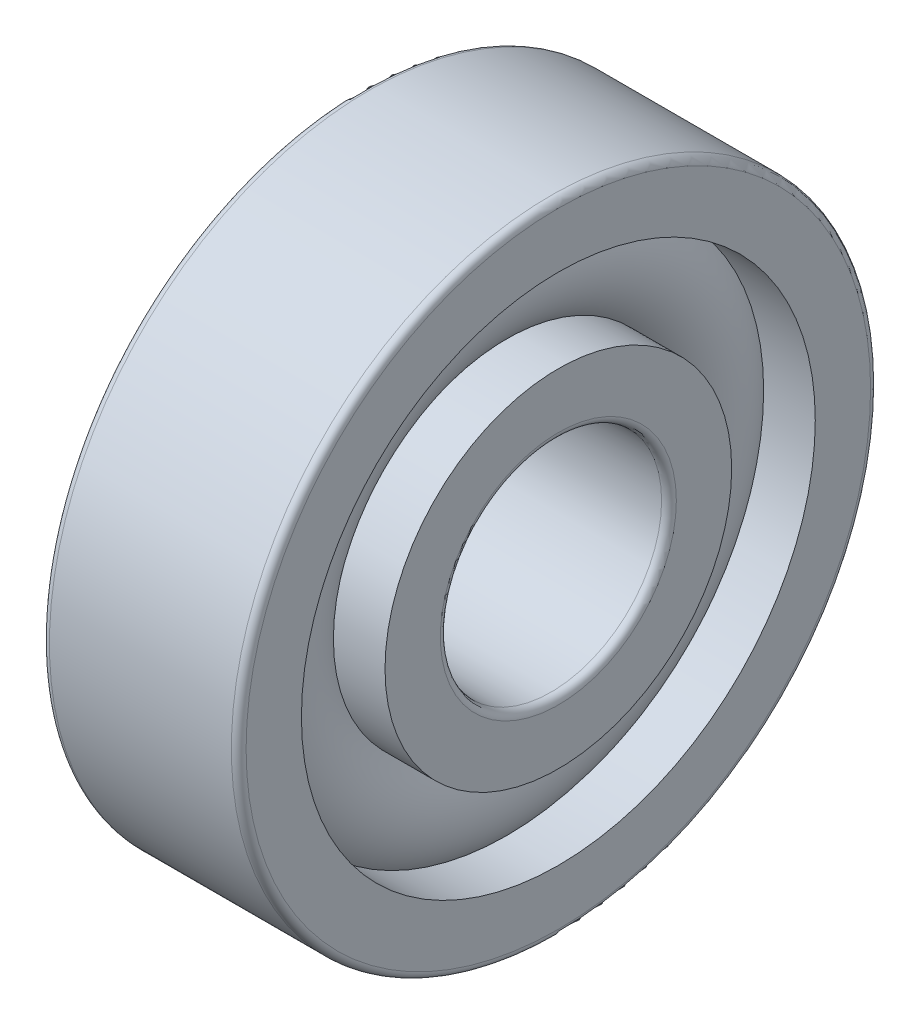
SolidWorks part; units mm, degrees
ref_plane "Plane1" through (0, 0, 0) normal (0, 0, 1) x (1, 0, 0)
ref_plane "Plane2" through (0, 0, 0) normal (0, 1, 0) x (1, 0, 0)
ref_plane "Plane3" through (0, 0, 0) normal (1, 0, 0) x (0, 0, -1)
other "Configuration Table"
sketch "Clipboard" plane through (0, 0, 0) normal (0, 0, 1) x (1, 0, 0)
  line L0 (-10, 0) -> (10, 0) construction
  line L1 (0, 0) -> (22.3471, -0.7804)
  line L2 (0, 0) -> (8.7447, 0.3054)
  line L3 (0, 0) -> (22.3471, -0.7804)
  line L4 (0, 0) -> (-22.3573, -0.3902)
  dimension "BallCLRad" = 8.75
sketch "CagSpiSke" plane through (0, 0, 0) normal (0, 0, 1) x (1, 0, 0)
  line L0 (0.255, 8.325) -> (0.255, 9.175)
  line L1 (0.255, 9.175) -> (-0.255, 9.175)
  line L2 (-0.255, 9.175) -> (-0.255, 8.325)
  line L3 (-0.255, 8.325) -> (0.255, 8.325)
  line L4 (-20.6375, 0) -> (20.6375, 0) construction
  line L5 (0, 0) -> (0, 23.7692) construction
  dimension "OD" = 18.35
  dimension "ID" = 16.65
revolve "CageSpine" add sketch "CagSpiSke" angle 0.001 about L4 reverse direction yes
ref_axis "Axis1" through (-50, 0, 0) along (1, 0, 0)
sketch "CagBalSke" plane through (0, 0, 0) normal (0, 0, 1) x (1, 0, 0)
  line L0 (-2.805, 8.75) -> (2.805, 8.75)
  line L1 (-1.905, 8.75) -> (1.905, 8.75) construction
  line L2 (-10, 0) -> (10, 0) construction
  line L3 (0, 0) -> (0, 24) construction
  arc A0 (2.805, 8.75) -> (-2.805, 8.75) centre (0, 8.75) cw
  dimension "BallCLRad" = 8.75
revolve "CageBall" [suppressed] add sketch "CagBalSke" angle 360 about L1 reverse direction yes
pattern_circular "CageBalls" [suppressed] count 2 every 180 about axis through (-50, 0, 0) along (1, 0, 0)
sketch "CagTrmODSke" plane through (0, 0, 0) normal (0, 0, 1) x (1, 0, 0)
  line L0 (2.806, 9.175) -> (2.806, 11.556)
  line L1 (2.806, 11.556) -> (-2.806, 11.556)
  line L2 (-2.806, 11.556) -> (-2.806, 9.175)
  line L3 (-2.806, 9.175) -> (2.806, 9.175)
  line L4 (-20.6375, 0) -> (20.6375, 0) construction
  line L5 (0, 0) -> (0, 25) construction
  dimension "Width" = 5.612
  dimension "ID" = 18.35
  dimension "OD" = 23.112
revolve "CageTrimOD" [suppressed] cut sketch "CagTrmODSke" angle 360 about L4 reverse direction yes
sketch "CagTrmIDSke" plane through (0, 0, 0) normal (0, 0, 1) x (1, 0, 0)
  line L0 (2.806, 5.946) -> (2.806, 8.325)
  line L1 (2.806, 8.325) -> (-2.806, 8.325)
  line L2 (-2.806, 8.325) -> (-2.806, 5.946)
  line L3 (-2.806, 5.946) -> (2.806, 5.946)
  line L4 (-20.6375, 0) -> (20.6375, 0) construction
  line L5 (0, 0) -> (0, 25) construction
  dimension "Width" = 5.612
  dimension "ID" = 11.892
  dimension "OD" = 16.65
revolve "CageTrimID" [suppressed] cut sketch "CagTrmIDSke" angle 360 about L4 reverse direction yes
sketch "BalSimSke" plane through (0, 0, 0) normal (0, 0, 1) x (1, 0, 0)
  line L0 (-10, 0) -> (10, 0) construction
  line L1 (-10, 8.75) -> (10, 8.75) construction
  line L2 (0, 0) -> (0, 23) construction
  circle A0 centre (0, 8.75) radius 2.55
  dimension "BallCLRad" = 8.75
  dimension "Ball_diameter" = 5.1
revolve "BallsSimplified" add sketch "BalSimSke" angle 360 about L0
sketch "BalDetSke" plane through (0, 0, 0) normal (0, 0, 1) x (1, 0, 0)
  line L0 (-2.55, 8.75) -> (2.55, 8.75)
  line L1 (-1.905, 8.75) -> (1.905, 8.75) construction
  line L2 (0, 0) -> (0, 25) construction
  arc A0 (2.55, 8.75) -> (-2.55, 8.75) centre (0, 8.75) cw
  dimension "BallCLRad" = 8.75
  dimension "Ball_diameter" = 5.1
revolve "BallDetailed" [suppressed] add sketch "BalDetSke" angle 360 about L1 reverse direction yes
sketch "InnRacSke" plane through (0, 0, 0) normal (0, 0, 1) x (1, 0, 0)
  line L0 (-1.867, 7.05) -> (-4, 7.05)
  line L1 (-4, 7.05) -> (-4, 4.8)
  line L2 (-3.7, 4.5) -> (3.7, 4.5)
  line L3 (4, 4.8) -> (4, 7.05)
  line L4 (4, 7.05) -> (1.867, 7.05)
  line L5 (-20.6375, 0) -> (20.6375, 0) construction
  line L6 (0, 0) -> (0, 30) construction
  arc A0 (-4, 4.8) -> (-3.7, 4.5) centre (-3.7, 4.8) ccw
  arc A1 (3.7, 4.5) -> (4, 4.8) centre (3.7, 4.8) ccw
  arc A2 (1.867, 7.05) -> (-1.867, 7.05) centre (0, 8.75) cw
  dimension "BallCLRad" = 8.75
  dimension "Fillet_radius" = 0.3
  dimension "Ball_diameter" = 5.05
  dimension "ID" = 9
  dimension "OD" = 14.1
  dimension "Width" = 8
revolve "InnerRace" add sketch "InnRacSke" angle 360 about L5 reverse direction yes
sketch "OutRacSke" plane through (0, 0, 0) normal (0, 0, 1) x (1, 0, 0)
  line L0 (-1.867, 10.45) -> (-4, 10.45)
  line L1 (-4, 10.45) -> (-4, 12.7)
  line L2 (-3.7, 13) -> (3.7, 13)
  line L3 (4, 12.7) -> (4, 10.45)
  line L4 (4, 10.45) -> (1.867, 10.45)
  line L5 (-20.6375, 0) -> (20.6375, 0) construction
  line L6 (0, 0) -> (0, 30) construction
  arc A0 (-4, 12.7) -> (-3.7, 13) centre (-3.7, 12.7) cw
  arc A1 (3.7, 13) -> (4, 12.7) centre (3.7, 12.7) cw
  arc A2 (1.867, 10.45) -> (-1.867, 10.45) centre (0, 8.75) ccw
  dimension "BallCLRad" = 8.75
  dimension "Fillet_radius" = 0.3
  dimension "Ball_diameter" = 5.05
  dimension "Width" = 8
revolve "OuterRace" add sketch "OutRacSke" angle 360 about L5 reverse direction yes
pattern_circular "BallsDetailed" [suppressed] count 2 every 180 about axis through (-50, 0, 0) along (1, 0, 0)
equation "\"BallCLRad@Clipboard\" = ( \"OD@OutRacSke\" + \"ID@InnRacSke\" ) / 4"
equation "\"BallCLRad@BalSimSke\" = \"BallCLRad@Clipboard\""
equation "\"BallCLRad@BalDetSke\" = \"BallCLRad@Clipboard\""
equation "\"BallCLRad@InnRacSke\" = \"BallCLRad@Clipboard\""
equation "\"BallCLRad@OutRacSke\" = \"BallCLRad@Clipboard\""
equation "\"Ball_diameter@InnRacSke\" = \"Ball_diameter@BalDetSke\" - 0.05"
equation "\"Ball_diameter@OutRacSke\" = \"Ball_diameter@BalDetSke\" - 0.05"
equation "\"Ball_diameter@BalSimSke\" = \"Ball_diameter@BalDetSke\""
equation "\"Width@OutRacSke\" = \"Width@InnRacSke\""
equation "\"Fillet_radius@OutRacSke\" = \"Fillet_radius@InnRacSke\""
equation "\"Max_count@Clipboard\" = int( 3.14159265 / atn(( \"Ball_diameter@BalDetSke\" / 2) / sqr( \"BallCLRad@Clipboard\"  *  \"BallCLRad@Clipboard\" - ( \"Ball_diameter@BalDetSke\" / 2) *  ( \"Ball_diameter@BalDetSke\" / 2))))"
equation "\"Max_count@Clipboard\" = ((sgn( \"Max_count@Clipboard\" - \"Count@Clipboard\" )-1)*( \"Max_count@Clipboard\" - \"Count@Clipboard\" ))/-2+ \"Count@Clipboard\""
equation "\"Count@BallsDetailed\" = int( \"Show_count@Clipboard\" ) "
equation "\"Count@BallsDetailed\" = ((sgn( \"Count@BallsDetailed\" - \"Max_count@Clipboard\" )-1)*( \"Count@BallsDetailed\" - \"Max_count@Clipboard\" ))/-2+ \"Max_count@Clipboard\""
equation "\"Count@BallsDetailed\" = ((sgn( \"Count@BallsDetailed\" - \"Min_count@Clipboard\" )+1)*( \"Count@BallsDetailed\" - \"Min_count@Clipboard\"))/2 +\"Min_count@Clipboard\""
equation "\"Angle@BallsDetailed\" = 360.0 / \"Max_count@Clipboard\""
equation "\"BallCLRad@CagBalSke\" = \"BallCLRad@Clipboard\""
equation "\"Count@CageBalls\" = \"Count@BallsDetailed\""
equation "\"Angle@CageBalls\" = \"Angle@BallsDetailed\""
equation "\"Angle@CageSpine\" =  \"Angle@CageBalls\" * ( \"Count@CageBalls\" -1 + int( \"Count@CageBalls\" / \"Max_count@Clipboard\" ) )  + 0.001 -  int( \"Count@CageBalls\" / \"Max_count@Clipboard\" ) * 0.001"
equation "\"Angle@CageSpine\" =  \"Angle@CageSpine\" * int( \"Min_count@Clipboard\" / 2) + int(1 / \"Min_count@Clipboard\")  * 0.001"
equation "\"CageWallOD@CagBalSke\" =  \"Ball_diameter@BalDetSke\" * 1.1"
equation "\"Thickness@CagSpiSke\" =  \"Ball_diameter@BalDetSke\" * 0.1"
equation "\"OD@CagTrmODSke\" = \"BallCLRad@Clipboard\" * 2 + \"CageWallOD@CagBalSke\" + 0.002"
equation "\"ID@CagTrmODSke\" = \"BallCLRad@Clipboard\" * 2 + \"Ball_diameter@BalDetSke\" / 6"
equation "\"OD@CagTrmIDSke\" = \"BallCLRad@Clipboard\" * 2 - \"Ball_diameter@BalDetSke\" / 6"
equation "\"ID@CagTrmIDSke\" = \"BallCLRad@Clipboard\" * 2 - \"CageWallOD@CagBalSke\" + 0.002"
equation "\"OD@CagSpiSke\" = \"ID@CagTrmODSke\""
equation "\"ID@CagSpiSke\" = \"OD@CagTrmIDSke\""
equation "\"Width@CagTrmODSke\" = \"CageWallOD@CagBalSke\" + 0.002"
equation "\"Width@CagTrmIDSke\" = \"CageWallOD@CagBalSke\" + 0.002"
